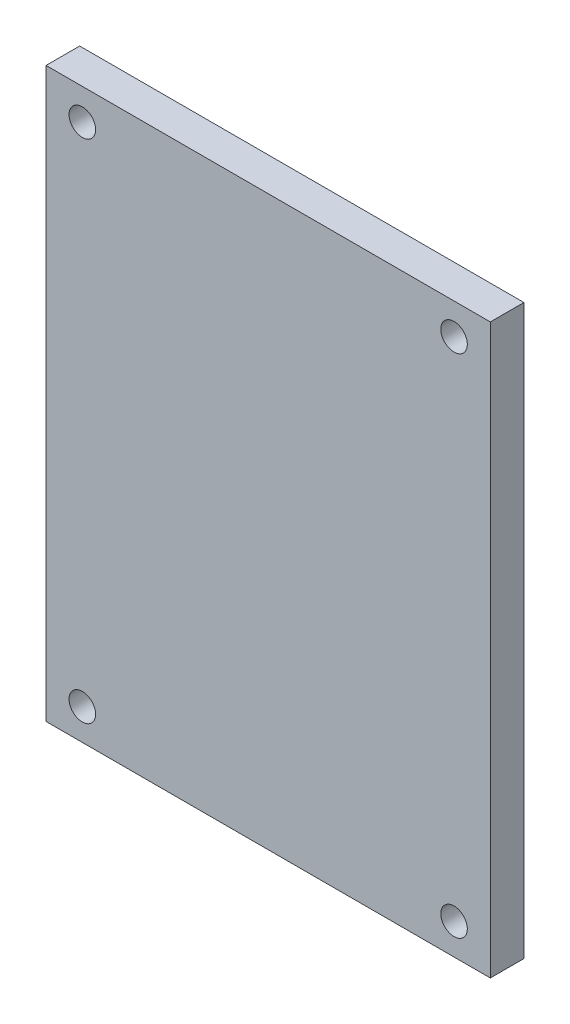
SolidWorks part; units mm, degrees
ref_plane "Front Plane" through (0, 0, 0) normal (0, 0, 1) x (1, 0, 0)
ref_plane "Top Plane" through (0, 0, 0) normal (0, 1, 0) x (1, 0, 0)
ref_plane "Right Plane" through (0, 0, 0) normal (1, 0, 0) x (0, 0, -1)
sketch "Sketch1" plane through (0, 0, 0) normal (0, 0, 1) x (1, 0, 0)
  line L0 (0, 40.767) -> (63.754, 40.767) construction
  line L1 (0, 0) -> (63.754, 0)
  line L2 (0, 0) -> (0, 81.534)
  line L3 (0, 81.534) -> (63.754, 81.534)
  line L4 (63.754, 0) -> (63.754, 81.534)
  line L5 (31.877, 81.534) -> (31.877, 0) construction
  circle A0 centre (5.207, 77.089) radius 1.905
  circle A1 centre (58.547, 77.089) radius 1.905
  circle A2 centre (5.207, 4.445) radius 1.905
  circle A3 centre (58.547, 4.445) radius 1.905
  dimension "D3" = 3.81
  dimension "D4" = 3.81
  dimension "D5" = 3.81
  dimension "D6" = 3.81
  dimension "D1" = 81.534
  dimension "D2" = 63.754
  dimension "D7" = 72.644
  dimension "D8" = 53.34
  dimension "D9" = 53.34
  dimension "D10" = 72.644
  dimension "D11" = 36.322
  dimension "D12" = 26.67
extrude "Boss-Extrude1" add sketch "Sketch1" along normal blind 4.826
equation "\"MDF\"= 0.19in"
equation "\"PVCID\" = 2.067in"
equation "\"PVCOD\" = 2.375in"
equation "\"GenDiameter\"= 60mm"
equation "\"GenCutDiameter\" = 1.8in"
equation "\"GenCutDistance\" = 1"
equation "\"TowerHeight\" = 6in"
equation "\"TowerFrontBase\" = 3in"
equation "\"FunnelHeight\" = 1in"
equation "\"FunnelAngle\" = 20"
equation "\"TowerSideBase\" = 3in"
equation "\"TowerPanelLength\" = 2in"
equation "\"TowerPanelLeeway\" = 0.5in"
equation "\"BaseLength\" = 9in"
equation "\"BaseWidth\" = 10in"
equation "\"WheelHoleLength\" = 3.25in"
equation "\"WheelHoleWidth\" = 26mm"
equation "\"WheelHoleFromBack\" = 1.5in"
equation "\"DropLength\" = 1in"
equation "\"DropWidth\" = 8.5in"
equation "\"BumperWidth\" = 2in"
equation "\"SmallHexDiameter\" = 0.185in"
equation "\"SmallHexHeight\" = 0.701in"
equation "\"ScrewSize\" = 0.106in"
equation "\"BigHexDiameter\" = 0.251in"
equation "\"BigHexHeight\" = 0.374in"
equation "\"PCBThickness\" = 0.066in"
equation "\"ConnectorHeight\" = 0.517in"
equation "\"BoardHeight\" = 0.583in"
equation "\"UnoStackHeight\" = 1.351in"
equation "\"UnoStackWidth\" = 3.053in"
equation "\"UnoStackLength\" = 3.152in"
equation "\"HBridgeWidth\" = 1.797in"
equation "\"HBridgeLength\" = 2.236in"
equation "\"DSWidth\" = 1.820in"
equation "\"DSLength\" = 1.833in"
equation "\"StepperWidth\" = 1.799in"
equation "\"StepperLength\" = 2.248in"
equation "\"ULNWidth\" = 1.304in"
equation "\"ULNLength\" = 1.545in"
equation "\"VSwitchHeight\" = 0.392in"
equation "\"VSwitchWidth\" = 0.637in"
equation "\"VSwitchLength\" = 1.097in"
equation "\"SkateWheelDiameter\" = 80mm"
equation "\"SkateWheelThickness\" = 24mm"
equation "\"BaseDistance\" = 3in"
equation "\"DummyVar\" = 2in"
equation "\"D1@Boss-Extrude1\"=\"MDF\""
